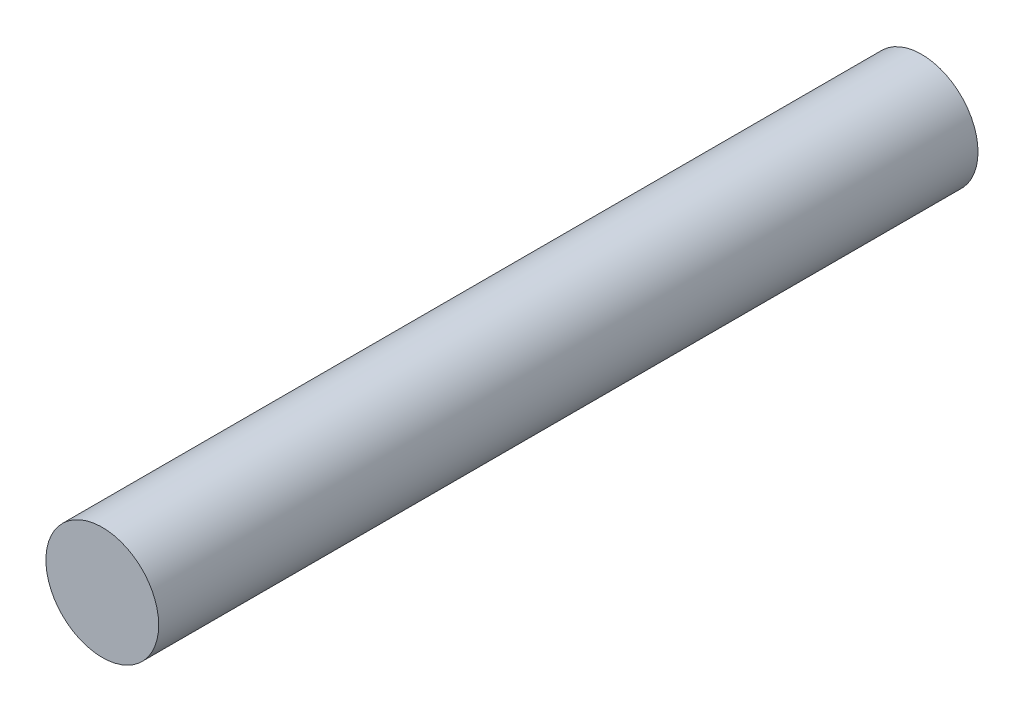
SolidWorks part; units mm, degrees
ref_plane "Front Plane" through (0, 0, 0) normal (0, 0, 1) x (1, 0, 0)
ref_plane "Top Plane" through (0, 0, 0) normal (0, 1, 0) x (1, 0, 0)
ref_plane "Right Plane" through (0, 0, 0) normal (1, 0, 0) x (0, 0, -1)
sketch "Sketch1" plane through (0, 0, 0) normal (0, 0, 1) x (1, 0, 0)
  circle A0 centre (0, 0) radius 9.017
  circle A1 centre (0, 0) radius 8.1
extrude "Boss-Extrude1" add sketch "Sketch1" along normal blind 130
sketch "Sketch2" plane through (0, 0, 130) normal (0, 0, 1) x (1, 0, 0)
  circle A0 centre (0, 0) radius 9.017
extrude "Boss-Extrude2" add sketch "Sketch2" along normal blind 1
